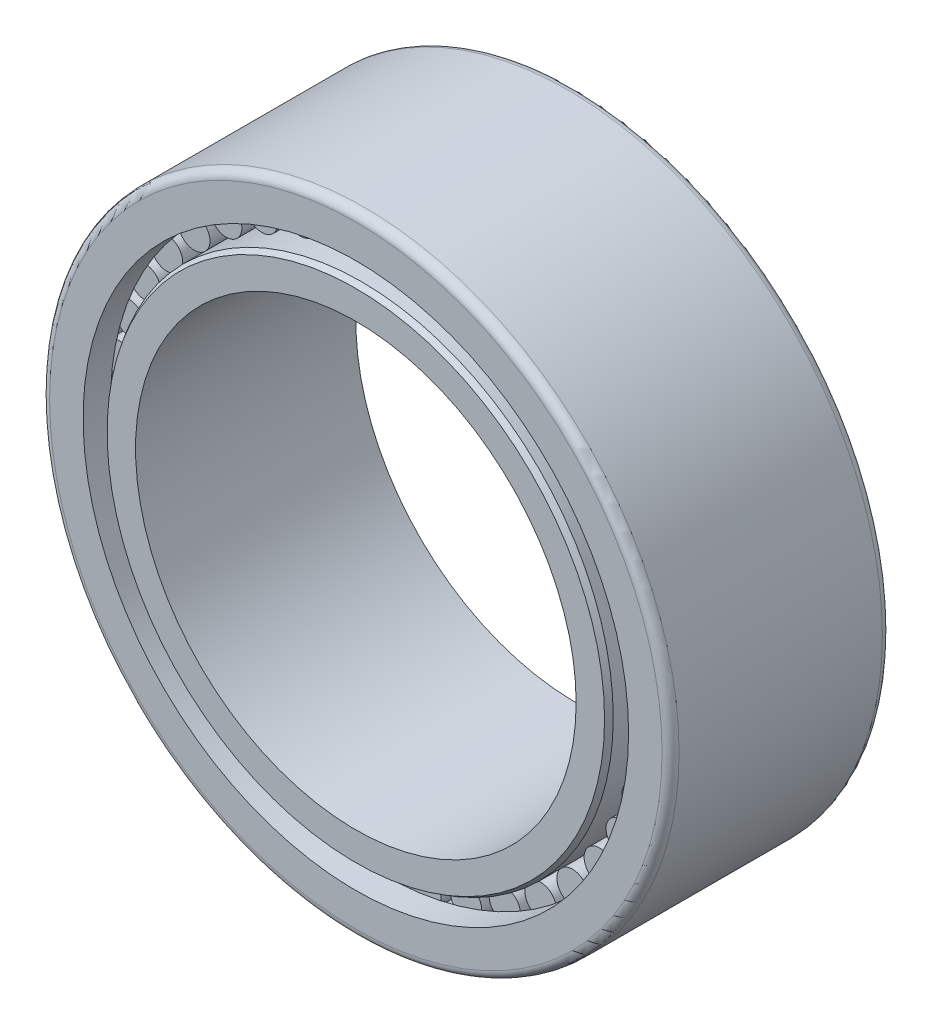
SolidWorks part; units mm, degrees
ref_plane "Front Plane" through (0, 0, 0) normal (0, 0, 1) x (1, 0, 0)
ref_plane "Top Plane" through (0, 0, 0) normal (0, 1, 0) x (1, 0, 0)
ref_plane "Right Plane" through (0, 0, 0) normal (1, 0, 0) x (0, 0, -1)
sketch "BaseSke" plane through (0, 0, 0) normal (1, 0, 0) x (0, 0, -1)
  line L0 (-47.2296, 0) -> (24.6132, 0) construction
  line L1 (-47.2296, 42.5) -> (24.6132, 42.5) construction
  line L2 (0, 129.5214) -> (0, -86.3012) construction
  line L3 (-13.125, 42.5) -> (-13.125, 45) construction
  line L4 (-17.5, 50) -> (17.5, 50) construction
  line L5 (-17.5, 35) -> (17.5, 35) construction
  line L6 (-13.125, 40) -> (13.125, 40)
  line L7 (-13.125, 40) -> (-13.125, 42.5)
  line L8 (-13.125, 42.5) -> (13.125, 42.5)
  line L9 (13.125, 40) -> (13.125, 42.5)
  line L10 (-13.125, 45) -> (13.125, 45) construction
  line L11 (13.125, 45) -> (13.125, 42.5) construction
  dimension "D2" = 26.25
  dimension "D1" = 85
revolve "Roller" add sketch "BaseSke" angle 360 about L8
sketch "OuterRaceSke" plane through (0, 0, 0) normal (1, 0, 0) x (0, 0, -1)
  line L0 (0, 0) -> (0, 87.5396) construction
  line L1 (-17.5, 50) -> (17.5, 50)
  line L2 (-17.5, 50) -> (-17.5, 43.3333)
  line L3 (-17.5, 43.3333) -> (-13.15, 43.3333)
  line L4 (17.5, 50) -> (17.5, 43.3333)
  line L5 (-50.3916, 0) -> (55.2197, 0) construction
  line L6 (-13.125, 45) -> (13.125, 45) construction
  line L7 (13.15, 43.3333) -> (17.5, 43.3333)
  line L9 (-13.15, 43.3333) -> (-13.15, 44.98)
  line L10 (-13.15, 44.98) -> (13.15, 44.98)
  line L11 (13.15, 43.3333) -> (13.15, 44.98)
  dimension "D2" = 86.6667
  dimension "D1" = 26.3
  dimension "D3" = 0.02
revolve "OuterRace" add sketch "OuterRaceSke" angle 360 about L5
sketch "InnerRaceSke" plane through (0, 0, 0) normal (1, 0, 0) x (0, 0, -1)
  line L0 (-70.8626, 0) -> (113.5527, 0) construction
  line L1 (0, 58.441) -> (0, -70.8113) construction
  line L2 (-17.5, 35) -> (17.5, 35)
  line L3 (-17.5, 35) -> (-17.5, 39.5148)
  line L5 (-16.625, 40.02) -> (-17.5, 39.5148)
  line L6 (0, 129.5214) -> (0, -86.3012) construction
  line L7 (-16.625, 40.02) -> (16.625, 40.02)
  line L9 (17.5, 35) -> (17.5, 39.5148)
  line L10 (16.625, 40.02) -> (17.5, 39.5148)
  line L13 (-13.125, 40) -> (13.125, 40) construction
  point P17 (0, 35)
  dimension "D1" = 33.25
  dimension "D2" = 0.02
  dimension "D3" = 30
revolve "InnerRace" add sketch "InnerRaceSke" angle 360 about L0
fillet "Fillet1" radius 1.35 2 edges at (50, 0, -17.5) (50, 0, 17.5)
pattern_circular "CirPatternBall" count 40 over 360 about axis through (0, 0, 50.3916) along (0, 0, -1) of "Roller"
sketch "SimplifiedSke" plane through (0, 0, 0) normal (1, 0, 0) x (0, 0, -1)
  line L0 (37.5911, 0) -> (-37.5911, 0) construction
  line L1 (-13.1351, 42.5) -> (13.151, 42.5) construction
  line L2 (-13.125, 45) -> (13.125, 45)
  line L3 (-13.125, 45) -> (-13.125, 40)
  line L4 (-13.125, 40) -> (13.125, 40)
  line L5 (13.125, 45) -> (13.125, 40)
  line L6 (-47.2296, 42.5) -> (24.6132, 42.5) construction
revolve "Simplified" [suppressed] add sketch "SimplifiedSke" angle 360 about L0
equation "\"D2@BaseSke\" = \"Bearing_Thickness@BaseSke\"*0.75"
equation "\"D1@BaseSke\" =  ( \"Bearing_Outside_Diameter@BaseSke\" + \"Bearing_Inside_Diameter@BaseSke\" )  / 2"
equation "\"D1@OuterRaceSke\" = \"Bearing_Thickness@BaseSke\"*0.75+0.05"
equation "\"D2@OuterRaceSke\" =  \"D1@BaseSke\" + ( \"D1@BaseSke\" - \"Diameter_Fw@BaseSke\" )  /3"
equation "\"D1@InnerRaceSke\" = \"Bearing_Thickness@BaseSke\"*0.95"
equation "\"D1@CirPatternBall\" =  int(  ( \"Bearing_Outside_Diameter@BaseSke\" + \"Bearing_Inside_Diameter@BaseSke\" )  / 2 *  pi  /  ( \"Bearing_Outside_Diameter@BaseSke\" - \"Bearing_Inside_Diameter@BaseSke\" ) * 4.5 ) "
